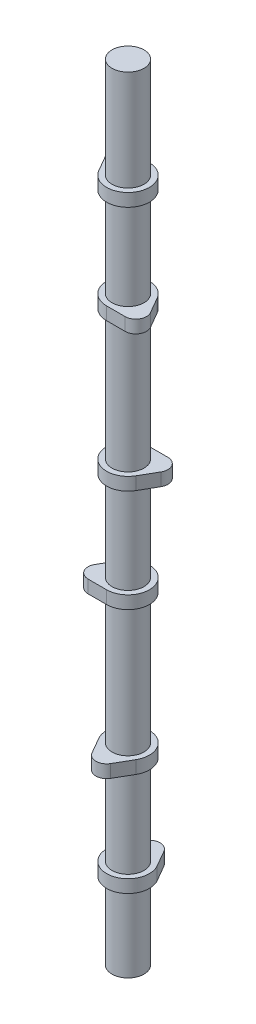
SolidWorks part; units mm, degrees
ref_plane "Front Plane" through (0, 0, 0) normal (0, 0, 1) x (1, 0, 0)
ref_plane "Top Plane" through (0, 0, 0) normal (0, 1, 0) x (1, 0, 0)
ref_plane "Right Plane" through (0, 0, 0) normal (1, 0, 0) x (0, 0, -1)
sketch "Sketch2" plane through (0, 0, 0) normal (0, 1, 0) x (1, 0, 0)
  line L0 (-5.4993, 15.875) -> (-10.9985, 6.35)
  line L1 (5.4993, 15.875) -> (10.9985, 6.35)
  arc A0 (-10.9985, 6.35) -> (10.9985, 6.35) centre (0, 0) ccw
  arc A1 (5.4993, 15.875) -> (-5.4993, 15.875) centre (0, 12.7) ccw
  dimension "D1" = 12.7
  dimension "D3" = 25.4
  dimension "D2" = 12.7
extrude "Boss-Extrude1" add sketch "Sketch2" along normal mid plane 7.62
ref_axis "Axis1" through (0, 85.2929, 0) along (0, -1, 0)
pattern_linear "LPattern1" count 2 spacing 60.96 along (0, 1, 0) of bodies 101
move or copy body "Body-Move/Copy1" bodies to move or copy 102 copy no rotation origin (0, 0, 0) rotation axis (0, 1, 0) rotation angle 180
pattern_linear "LPattern2" count 3 spacing 146.05 along (0, 1, 0) of bodies 101 103
move or copy body "Body-Move/Copy2" bodies to move or copy 104 106 copy no rotation origin (0, 0, 0) rotation axis (0, 1, 0) rotation angle 120
move or copy body "Body-Move/Copy3" bodies to move or copy 107 105 copy no rotation origin (0, 0, 0) rotation axis (0, -1, 0) rotation angle 120
sketch "Sketch5" plane through (0, 0, 0) normal (0, 1, 0) x (1, 0, 0)
  circle A0 centre (0, 0) radius 9.5
  dimension "D1" = 19
extrude "Boss-Extrude2" add sketch "Sketch5" along normal blind 466.09 from offset 49.53 offset against normal yes
